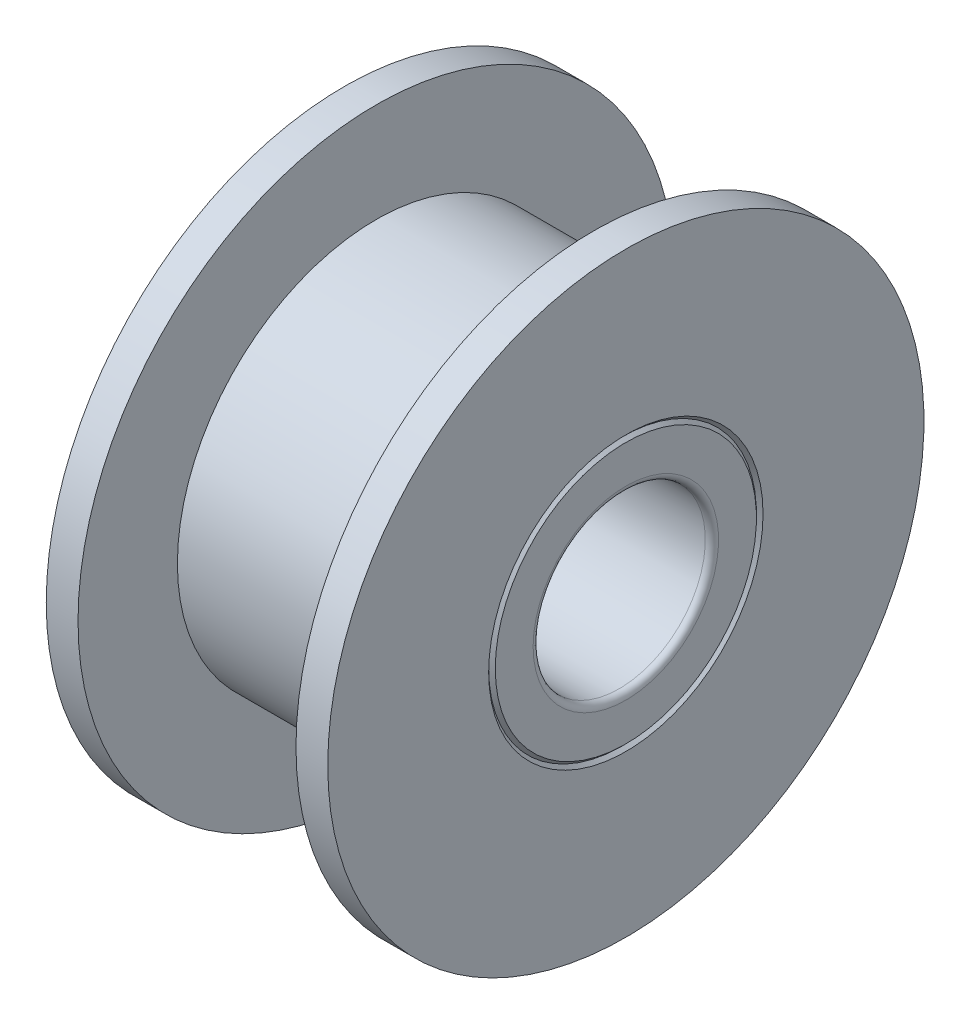
SolidWorks part; units mm, degrees
material "1.2311 (40CrMnMo7)"
ref_plane "Front" through (0, 0, 0) normal (0, 0, 1) x (1, 0, 0)
ref_plane "Top" through (0, 0, 0) normal (0, 1, 0) x (1, 0, 0)
ref_plane "Right" through (0, 0, 0) normal (1, 0, 0) x (0, 0, -1)
sketch "Sketch 1" plane through (0, 0, 0) normal (0, 0, 1) x (1, 0, 0)
  line L0 (5.5, 7.5) -> (5.5, 2.6424)
  line L1 (1, -1.5) -> (14, -1.5) construction
  line L2 (5.5, 7.5) -> (6.46, 7.5)
  line L4 (6.46, 4.5) -> (13.04, 4.5)
  line L5 (13.04, 4.5) -> (13.04, 7.5)
  line L6 (13.04, 7.5) -> (14, 7.5)
  line L7 (14, 1.1) -> (14, 2.4424)
  line L8 (14, 2.4424) -> (13.9, 2.5424)
  line L9 (13.9, 2.5424) -> (14, 2.6424)
  line L10 (14, 2.6424) -> (14, 7.5)
  line L11 (14, 1.1) -> (5.5, 1.1)
  line L12 (6.46, 7.5) -> (6.46, 4.5)
  line L14 (5.5, 2.3576) -> (5.6035, 2.5)
  line L15 (5.6035, 2.5) -> (5.5, 2.6424)
  line L16 (5.5, 2.3576) -> (5.5, 1.1)
  dimension "D1" = 6
  dimension "D2" = 0.96
  dimension "D3" = 2.6
  dimension "D4" = 8.5
  dimension "D5" = 0.1
  dimension "D6" = 5
  dimension "D7" = 9
revolve "Body" add sketch "Sketch 1" angle 360 about L1 region at (9.7506, 3.3324, 0)
sketch "Sketch 3" plane through (6.46, 0, 0) normal (1, 0, 0) x (0, 0, -1)
  line L0 (0, 0) -> (9.7637, 0) construction
  circle A18 centre (0, 5.855) radius 0.55
  point P45 (0, 0)
ref_axis "Axis1" through (-2.8, 0, 0) along (1, 0, 0)
fillet "Fillet1" radius 0.2 2 edges at (14, -1.5, 2.6) (5.5, -1.5, 2.6)
sketch "Sketch1" plane through (14, 0, 0) normal (1, 0, 0) x (0, 0, -1)
  point P0 (0, -1.5)
